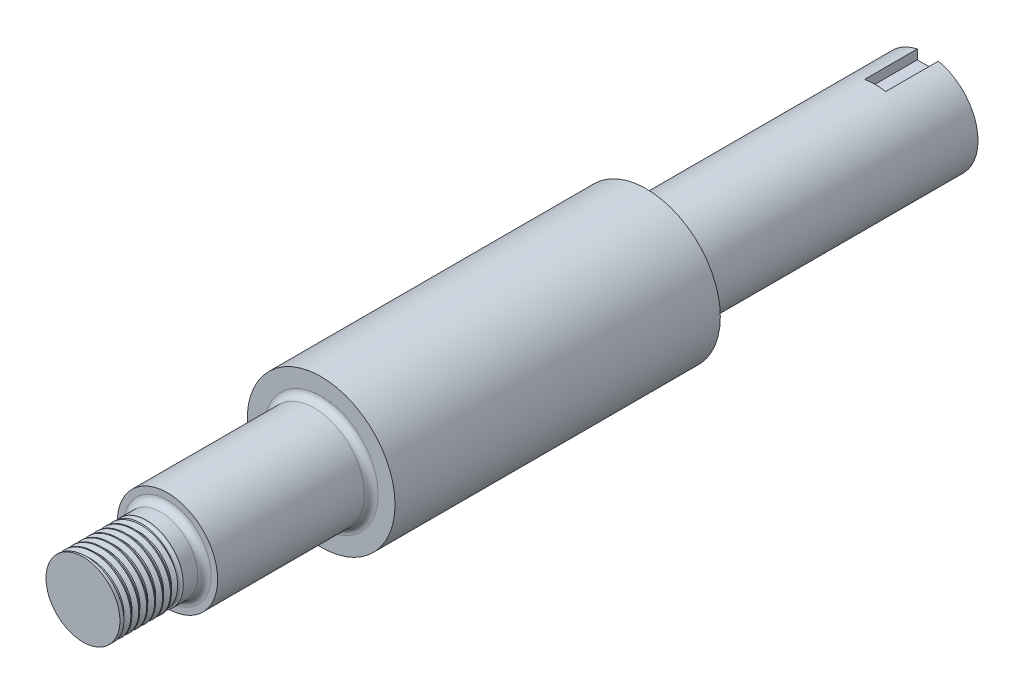
SolidWorks part; units mm, degrees
material "AISI 1020"
ref_plane "Front Plane" through (0, 0, 0) normal (0, 0, 1) x (1, 0, 0)
ref_plane "Top Plane" through (0, 0, 0) normal (0, 1, 0) x (1, 0, 0)
ref_plane "Right Plane" through (0, 0, 0) normal (1, 0, 0) x (0, 0, -1)
sketch "Sketch Spindle Skeleton" plane through (0, 0, 0) normal (1, 0, 0) x (0, 0, -1)
  line L0 (-114.9, -9.5) -> (-144, -9.5)
  line L5 (-1000, 0) -> (49000, 0)
  line L6 (0, -9.5) -> (0, 9.5)
  line L13 (0, 9.5) -> (-53.3, 9.5)
  line L26 (-53.3, 9.5) -> (-53.3, 14)
  line L27 (-53.3, 14) -> (-114.9, 14)
  line L32 (-114.9, 14) -> (-114.9, 9.5)
  line L34 (-160, 7) -> (-160, -7)
  line L36 (-114.9, -9.5) -> (-114.9, -14)
  line L37 (-114.9, -14) -> (-53.3, -14)
  line L38 (-53.3, -14) -> (-53.3, -9.5)
  line L39 (0, -9.5) -> (-53.3, -9.5)
  line L40 (-21.7, 36) -> (-14.7, 36)
  line L41 (-131.5, 22.6312) -> (-114.9, 22.6312)
  line L42 (-131.5, 22.6312) -> (-131.5, -22.6312)
  line L43 (-131.5, -22.6312) -> (-114.9, -22.6312)
  line L44 (-114.9, 22.6312) -> (-114.9, -22.6312)
  line L45 (-131.5, 22.6312) -> (-114.9, -22.6312) construction
  line L46 (-131.5, -22.6312) -> (-114.9, 22.6312) construction
  line L47 (-36.7, 22.6312) -> (-53.3, 22.6312)
  line L48 (-36.7, 22.6312) -> (-36.7, -22.6312)
  line L49 (-36.7, -22.6312) -> (-53.3, -22.6312)
  line L50 (-53.3, 22.6312) -> (-53.3, -22.6312)
  line L51 (-36.7, 22.6312) -> (-53.3, -22.6312) construction
  line L52 (-36.7, -22.6312) -> (-53.3, 22.6312) construction
  line L59 (-14.7, 36) -> (-14.7, -36)
  line L60 (-14.7, -36) -> (-21.7, -36)
  line L61 (-21.7, -22.6312) -> (-26.7, -22.6312)
  line L62 (-26.7, -22.6312) -> (-26.7, -12.6312)
  line L63 (-26.7, -12.6312) -> (-21.7, -12.6312)
  line L64 (-21.7, -12.6312) -> (-21.7, 12.6312)
  line L65 (-21.7, 12.6312) -> (-26.7, 12.6312)
  line L66 (-26.7, 12.6312) -> (-26.7, 22.6312)
  line L67 (-26.7, 22.6312) -> (-21.7, 22.6312)
  line L68 (-21.7, 22.6312) -> (-21.7, 36)
  line L69 (-21.7, -22.6312) -> (-21.7, -36)
  line L71 (-133.659, 36) -> (-22.7, 36)
  line L72 (-133.659, 36) -> (-133.659, -36)
  line L73 (-133.659, -36) -> (-22.7, -36)
  line L74 (-22.7, 36) -> (-22.7, -36)
  line L75 (-133.659, 36) -> (-22.7, -36) construction
  line L76 (-133.659, -36) -> (-22.7, 36) construction
  line L77 (-144, -9.5) -> (-144, -7)
  line L78 (-144, -7) -> (-160, -7)
  line L79 (-114.9, 9.5) -> (-144, 9.5)
  line L80 (-144, 7) -> (-160, 7)
  line L81 (-144, 9.5) -> (-144, 7)
  line L82 (-129.45, 9.5) -> (-129.45, -9.5) construction
  line L83 (-26.65, 9.5) -> (-26.65, -9.5) construction
  line L96 (-133.659, 36) -> (-140.659, 36)
  line L98 (-133.659, -36) -> (-140.659, -36)
  line L99 (-140.659, 36) -> (-140.659, -36)
  line L110 (-133.659, 36) -> (-133.659, -36)
  point P3 (0, 0)
  point P18 (-123.2, 0)
  point P24 (-45, 0)
  point P29 (-78.1795, 0)
  point P48 (-14.7, 29.3156)
  point P58 (0, 0)
  point P70 (-140.659, 29.3156)
revolve "Revolve Spindle" add sketch "Sketch Spindle Skeleton" angle 360 about L5
fillet "Bearing Rest Fillet 0.13cm " radius 1.3 3 edges at (9.5, 0, 53.3) (9.5, 0, 114.9) (7, 0, 144)
thread "Chuck Thread" pitch 1.5 start angle 0, offset 0, length 10, pitch 1.5, diameter 14
ref_plane "Plane2" through (-7, 0, 160) normal (0, -1, 0) x (-1, 0, 0)
sketch "Thread Profile2" plane through (-7, 0, 160) normal (0, -1, 0) x (-1, 0, 0)
  line L0 (0, 0) -> (0, 1.5) construction
  line L11 (0, 0) -> (0, 1.3125)
  line L12 (0, 1.3125) -> (-0.8119, 0.8437)
  line L13 (-0.8119, 0.8437) -> (-0.8119, 0.4687)
  line L15 (-0.8119, 0.4687) -> (0, 0)
  line L17 (-0.8119, 0.6562) -> (0, 0.6562) construction
  point P2 (0, 0)
  dimension "Pitch" = 1.5
  dimension "Profile_Angle" = 60
  dimension "Profile_Land" = 0.375
  dimension "Profile_Height" = 0.8119
sketch "Thread Slot Sketch" plane through (0, 0, 0) normal (1, 0, 0) x (0, 0, -1)
  line L0 (-148.6882, -6.0622) -> (-150.0007, -6.0622) construction
  line L1 (-148.6882, -6.0622) -> (-150.0007, -6.0622)
  line L5 (-145.3, 7) -> (-149.3125, 7) construction
  line L6 (-160, 7) -> (-160, -7) construction
  circle A0 centre (-148.5, 7) radius 0.5
  dimension "D1" = 1
  dimension "D2" = 11.5
revolve "Thread Slot" cut sketch "Thread Slot Sketch" angle 360 about L5
sketch "Sketch Key" plane through (0, 0, 0) normal (0, 0, -1) x (-1, 0, 0)
  line L0 (0, 8.5) -> (0, 0) construction
  line L1 (-2, 7.5) -> (2, 7.5)
  line L2 (-2, 7.5) -> (-2, 9.5)
  line L3 (-2, 9.5) -> (2, 9.5)
  line L4 (2, 7.5) -> (2, 9.5)
  line L5 (-2, 7.5) -> (2, 9.5) construction
  line L6 (-2, 9.5) -> (2, 7.5) construction
  circle A1 centre (0, 0) radius 9.5
  circle A2 centre (0, 0) radius 9.5
  point P0 (0, 8.5)
  dimension "D2" = 4
  dimension "D3" = 2
  dimension "D1" = 0
extrude "Key Cut" cut sketch "Sketch Key" against normal blind 10 contours L3 L4 L1 L2
